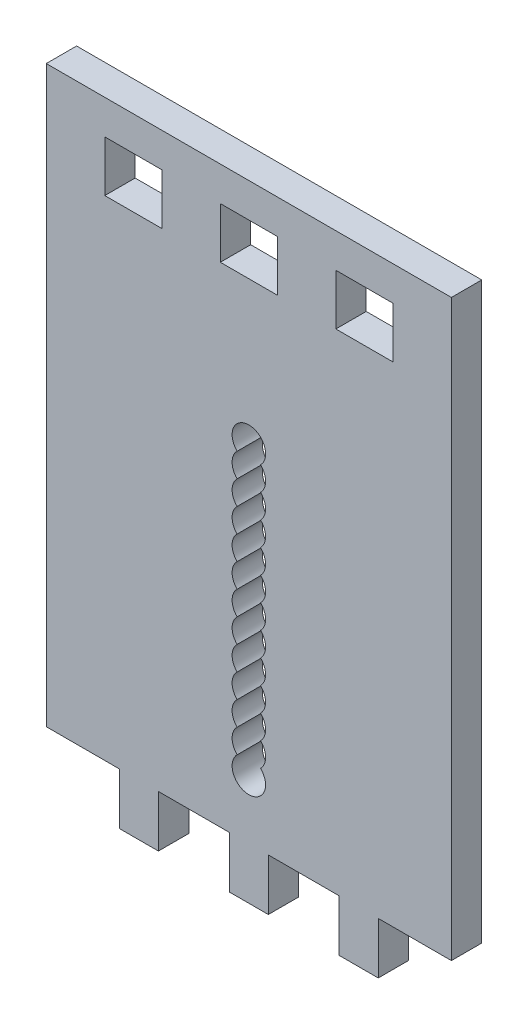
SolidWorks part; units mm, degrees
ref_plane "Front Plane" through (0, 0, 0) normal (0, 0, 1) x (1, 0, 0)
ref_plane "Top Plane" through (0, 0, 0) normal (0, 1, 0) x (1, 0, 0)
ref_plane "Right Plane" through (0, 0, 0) normal (1, 0, 0) x (0, 0, -1)
sketch "Sketch1" plane through (0, 0, 0) normal (0, 0, 1) x (1, 0, 0)
  line L0 (-21.15, 21.15) -> (21.15, 21.15) construction
  line L1 (-21.15, 38.85) -> (21.15, 38.85)
  line L2 (-21.15, 38.85) -> (-21.15, -21.15)
  line L3 (-21.15, -21.15) -> (21.15, -21.15)
  line L4 (21.15, 38.85) -> (21.15, -21.15)
  line L5 (2, -26.55) -> (2, -21.15)
  line L6 (-13.5, -21.15) -> (-9.5, -21.15)
  line L7 (-13.5, -21.15) -> (-13.5, -26.55)
  line L8 (-13.5, -26.55) -> (-9.5, -26.55)
  line L9 (-9.5, -21.15) -> (-9.5, -26.55)
  line L10 (2, -26.55) -> (-2, -26.55)
  line L11 (2, -21.15) -> (-2, -21.15)
  line L12 (-2, -26.55) -> (-2, -21.15)
  line L13 (2, -26.55) -> (-2, -21.15) construction
  line L14 (2, -21.15) -> (-2, -26.55) construction
  line L15 (-21.15, 8.85) -> (21.15, 8.85) construction
  line L16 (13.5, -21.15) -> (9.5, -21.15)
  line L17 (13.5, -21.15) -> (13.5, -26.55)
  line L18 (13.5, -26.55) -> (9.5, -26.55)
  line L19 (9.5, -21.15) -> (9.5, -26.55)
  line L21 (-15.1071, 35.35) -> (-9.0643, 35.35)
  line L22 (-15.1071, 35.35) -> (-15.1071, 29.95)
  line L23 (-15.1071, 29.95) -> (-9.0643, 29.95)
  line L24 (-9.0643, 35.35) -> (-9.0643, 29.95)
  line L25 (-3.0214, 35.35) -> (3.0214, 35.35)
  line L26 (-3.0214, 35.35) -> (-3.0214, 29.95)
  line L27 (-3.0214, 29.95) -> (3.0214, 29.95)
  line L28 (3.0214, 35.35) -> (3.0214, 29.95)
  line L29 (9.0643, 35.35) -> (15.1071, 35.35)
  line L30 (9.0643, 35.35) -> (9.0643, 29.95)
  line L31 (9.0643, 29.95) -> (15.1071, 29.95)
  line L32 (0, 15) -> (0, -15) construction
  line L33 (-0.75, 15) -> (0.75, 15)
  line L34 (-0.75, 15) -> (-0.75, -15)
  line L35 (-0.75, -15) -> (0.75, -15)
  line L36 (0.75, 15) -> (0.75, -15)
  line L37 (15.1071, 35.35) -> (15.1071, 29.95)
  arc A1 (-0.75, 15) -> (0.75, 15) centre (0, 15) cw
  arc A2 (0.75, -15) -> (-0.75, -15) centre (0, -15) cw
  circle A3 centre (0, 15) radius 1.75
  circle A4 centre (0, 12.5) radius 1.75
  circle A5 centre (0, 10) radius 1.75
  circle A6 centre (0, 7.5) radius 1.75
  circle A7 centre (0, 5) radius 1.75
  circle A8 centre (0, 2.5) radius 1.75
  circle A9 centre (0, 0) radius 1.75
  circle A10 centre (0, -2.5) radius 1.75
  circle A11 centre (0, -5) radius 1.75
  circle A12 centre (0, -7.5) radius 1.75
  circle A13 centre (0, -10) radius 1.75
  circle A14 centre (0, -12.5) radius 1.75
  circle A15 centre (0, -15) radius 1.75
  point P13 (0, -21.15)
  point P14 (0, -23.85)
  dimension "D15" = 3.5
  dimension "D1" = 42.3
  dimension "D3" = 42.3
  dimension "D4" = 21.15
  dimension "D5" = 21.15
  dimension "D2" = 60
  dimension "D8" = 4
  dimension "D6" = 1.5
  dimension "D11" = 0.75
  dimension "D12" = 30
  dimension "D13" = 15
  dimension "D7" = 7.5
  dimension "D10" = 7.5
  dimension "D16" = 2.5
  dimension "D18" = 2.5
  dimension "D9" = 5.4
  dimension "D19" = 5.4
  dimension "D20" = 6.0429
  dimension "D21" = 6.0429
  dimension "D22" = 6.0429
  dimension "D23" = 6.0429
  dimension "D24" = 3.5
  dimension "D14" = 10
  dimension "D17" = 4
extrude "Boss-Extrude1" add sketch "Sketch1" along normal blind 3.175 contours L4 L1 L2 L3 L36 A2 L34 A1 | L1 | L1 | L1 | L9 L3 L7 L8 | L3 L19 L18 L17 | L12 L10 L5 L3 region at (0, 38.1159, 0) region at (-11.5, -23.85, 0) region at (11.5, -23.85, 0) region at (0, -23.85, 0)
sketch "Sketch2" plane through (0, 0, 3.175) normal (0, 0, 1) x (1, 0, 0)
  line L2 (-15.1071, 35.3094) -> (-9.0643, 35.3094)
  line L3 (-15.1071, 35.3094) -> (-9.0643, 35.3094)
  line L5 (-15.0665, 35.35) -> (-15.0665, 29.95)
  line L6 (-15.0665, 35.35) -> (-15.0665, 29.95)
  line L7 (9.1049, 35.35) -> (9.1049, 29.95)
  line L8 (-15.1071, 29.9906) -> (-9.0643, 29.9906)
  line L9 (-15.1071, 29.9906) -> (-9.0643, 29.9906)
  line L10 (9.1049, 35.35) -> (9.1049, 29.95)
  line L11 (-9.1049, 35.35) -> (-9.1049, 29.95)
  line L12 (-9.1049, 35.35) -> (-9.1049, 29.95)
  line L14 (-2.9808, 35.35) -> (-2.9808, 29.95)
  line L15 (-2.9808, 35.35) -> (-2.9808, 29.95)
  line L16 (9.0643, 35.3094) -> (15.1071, 35.3094)
  line L17 (9.0643, 35.3094) -> (15.1071, 35.3094)
  line L18 (-3.0214, 35.3094) -> (3.0214, 35.3094)
  line L19 (-3.0214, 35.3094) -> (3.0214, 35.3094)
  line L21 (-3.0214, 29.9906) -> (3.0214, 29.9906)
  line L22 (-3.0214, 29.9906) -> (3.0214, 29.9906)
  line L24 (2.9808, 35.35) -> (2.9808, 29.95)
  line L25 (2.9808, 35.35) -> (2.9808, 29.95)
  line L26 (9.0643, 29.9906) -> (15.1071, 29.9906)
  line L27 (9.0643, 29.9906) -> (15.1071, 29.9906)
  line L29 (15.0665, 35.35) -> (15.0665, 29.95)
  line L30 (15.0665, 35.35) -> (15.0665, 29.95)
  line L32 (21.1906, -21.1906) -> (21.1906, 38.8906)
  line L33 (21.1906, 38.8906) -> (-21.1906, 38.8906)
  line L34 (-21.1906, 38.8906) -> (-21.1906, -21.1906)
  line L35 (-21.1906, -21.1906) -> (-13.5406, -21.1906)
  line L36 (-13.5406, -21.1906) -> (-13.5406, -26.5906)
  line L37 (-13.5406, -26.5906) -> (-9.4594, -26.5906)
  line L38 (-9.4594, -26.5906) -> (-9.4594, -21.1906)
  line L39 (-9.4594, -21.1906) -> (-2.0406, -21.1906)
  line L40 (-2.0406, -21.1906) -> (-2.0406, -26.5906)
  line L41 (-2.0406, -26.5906) -> (2.0406, -26.5906)
  line L42 (2.0406, -26.5906) -> (2.0406, -21.1906)
  line L43 (2.0406, -21.1906) -> (9.4594, -21.1906)
  line L44 (9.4594, -21.1906) -> (9.4594, -26.5906)
  line L45 (9.4594, -26.5906) -> (13.5406, -26.5906)
  line L46 (13.5406, -26.5906) -> (13.5406, -21.1906)
  line L47 (13.5406, -21.1906) -> (21.1906, -21.1906)
  line L48 (21.1906, -21.1906) -> (21.1906, 38.8906)
  line L49 (21.1906, 38.8906) -> (-21.1906, 38.8906)
  line L50 (-21.1906, 38.8906) -> (-21.1906, -21.1906)
  line L51 (-21.1906, -21.1906) -> (-13.5406, -21.1906)
  line L52 (-13.5406, -21.1906) -> (-13.5406, -26.5906)
  line L53 (-13.5406, -26.5906) -> (-9.4594, -26.5906)
  line L54 (-9.4594, -26.5906) -> (-9.4594, -21.1906)
  line L55 (-9.4594, -21.1906) -> (-2.0406, -21.1906)
  line L56 (-2.0406, -21.1906) -> (-2.0406, -26.5906)
  line L57 (-2.0406, -26.5906) -> (2.0406, -26.5906)
  line L58 (2.0406, -26.5906) -> (2.0406, -21.1906)
  line L59 (2.0406, -21.1906) -> (9.4594, -21.1906)
  line L60 (9.4594, -21.1906) -> (9.4594, -26.5906)
  line L61 (9.4594, -26.5906) -> (13.5406, -26.5906)
  line L62 (13.5406, -26.5906) -> (13.5406, -21.1906)
  line L63 (13.5406, -21.1906) -> (21.1906, -21.1906)
  arc A2 (1.2247, 13.75) -> (-1.2247, 13.75) centre (0, 15) ccw
  arc A3 (1.2247, 13.75) -> (-1.2247, 13.75) centre (0, 15) ccw
  arc A5 (-1.2247, 13.75) -> (-1.2247, 11.25) centre (0, 12.5) ccw
  arc A6 (-1.2247, 13.75) -> (-1.2247, 11.25) centre (0, 12.5) ccw
  arc A8 (1.2247, 11.25) -> (1.2247, 13.75) centre (0, 12.5) ccw
  arc A9 (1.2247, 11.25) -> (1.2247, 13.75) centre (0, 12.5) ccw
  arc A11 (-1.2247, 11.25) -> (-1.2247, 8.75) centre (0, 10) ccw
  arc A12 (-1.2247, 11.25) -> (-1.2247, 8.75) centre (0, 10) ccw
  arc A14 (1.2247, 8.75) -> (1.2247, 11.25) centre (0, 10) ccw
  arc A15 (1.2247, 8.75) -> (1.2247, 11.25) centre (0, 10) ccw
  arc A17 (-1.2247, 8.75) -> (-1.2247, 6.25) centre (0, 7.5) ccw
  arc A18 (-1.2247, 8.75) -> (-1.2247, 6.25) centre (0, 7.5) ccw
  arc A20 (1.2247, 6.25) -> (1.2247, 8.75) centre (0, 7.5) ccw
  arc A21 (1.2247, 6.25) -> (1.2247, 8.75) centre (0, 7.5) ccw
  arc A23 (-1.2247, 6.25) -> (-1.2247, 3.75) centre (0, 5) ccw
  arc A24 (-1.2247, 6.25) -> (-1.2247, 3.75) centre (0, 5) ccw
  arc A26 (1.2247, 3.75) -> (1.2247, 6.25) centre (0, 5) ccw
  arc A27 (1.2247, 3.75) -> (1.2247, 6.25) centre (0, 5) ccw
  arc A29 (-1.2247, 3.75) -> (-1.2247, 1.25) centre (0, 2.5) ccw
  arc A30 (-1.2247, 3.75) -> (-1.2247, 1.25) centre (0, 2.5) ccw
  arc A32 (1.2247, 1.25) -> (1.2247, 3.75) centre (0, 2.5) ccw
  arc A33 (1.2247, 1.25) -> (1.2247, 3.75) centre (0, 2.5) ccw
  arc A35 (-1.2247, 1.25) -> (-1.2247, -1.25) centre (0, 0) ccw
  arc A36 (-1.2247, 1.25) -> (-1.2247, -1.25) centre (0, 0) ccw
  arc A38 (1.2247, -1.25) -> (1.2247, 1.25) centre (0, 0) ccw
  arc A39 (1.2247, -1.25) -> (1.2247, 1.25) centre (0, 0) ccw
  arc A42 (1.2247, -3.75) -> (1.2247, -1.25) centre (0, -2.5) ccw
  arc A43 (1.2247, -3.75) -> (1.2247, -1.25) centre (0, -2.5) ccw
  arc A45 (-1.2247, -1.25) -> (-1.2247, -3.75) centre (0, -2.5) ccw
  arc A46 (-1.2247, -1.25) -> (-1.2247, -3.75) centre (0, -2.5) ccw
  arc A48 (-1.2247, -3.75) -> (-1.2247, -6.25) centre (0, -5) ccw
  arc A49 (-1.2247, -3.75) -> (-1.2247, -6.25) centre (0, -5) ccw
  arc A51 (1.2247, -6.25) -> (1.2247, -3.75) centre (0, -5) ccw
  arc A52 (1.2247, -6.25) -> (1.2247, -3.75) centre (0, -5) ccw
  arc A55 (-1.2247, -6.25) -> (-1.2247, -8.75) centre (0, -7.5) ccw
  arc A56 (-1.2247, -6.25) -> (-1.2247, -8.75) centre (0, -7.5) ccw
  arc A58 (1.2247, -8.75) -> (1.2247, -6.25) centre (0, -7.5) ccw
  arc A59 (1.2247, -8.75) -> (1.2247, -6.25) centre (0, -7.5) ccw
  arc A61 (-1.2247, -8.75) -> (-1.2247, -11.25) centre (0, -10) ccw
  arc A62 (-1.2247, -8.75) -> (-1.2247, -11.25) centre (0, -10) ccw
  arc A64 (1.2247, -11.25) -> (1.2247, -8.75) centre (0, -10) ccw
  arc A65 (1.2247, -11.25) -> (1.2247, -8.75) centre (0, -10) ccw
  arc A67 (-1.2247, -11.25) -> (-1.2247, -13.75) centre (0, -12.5) ccw
  arc A68 (-1.2247, -11.25) -> (-1.2247, -13.75) centre (0, -12.5) ccw
  arc A70 (1.2247, -13.75) -> (1.2247, -11.25) centre (0, -12.5) ccw
  arc A71 (1.2247, -13.75) -> (1.2247, -11.25) centre (0, -12.5) ccw
  arc A73 (-1.2247, -13.75) -> (1.2247, -13.75) centre (0, -15) ccw
  arc A74 (-1.2247, -13.75) -> (1.2247, -13.75) centre (0, -15) ccw
  dimension "D1" = 0.0406
  dimension "D2" = 0.0406
  dimension "D3" = 0.0406
  dimension "D4" = 0.0406
  dimension "D5" = 0.0406
  dimension "D6" = 0.0406
  dimension "D7" = 0.0406
  dimension "D8" = 0.0406
  dimension "D9" = 0.0406
  dimension "D10" = 0.0406
  dimension "D11" = 0.0406
  dimension "D12" = 0.0406
  dimension "D13" = 0.0406
  dimension "D14" = 0
  dimension "D15" = 0
  dimension "D16" = 0
  dimension "D17" = 0
  dimension "D18" = 0
  dimension "D19" = 0
  dimension "D20" = 0
  dimension "D21" = 0
  dimension "D22" = 0
  dimension "D23" = 0
  dimension "D24" = 0
  dimension "D25" = 0
  dimension "D26" = 0
  dimension "D27" = 0
  dimension "D28" = 0
  dimension "D29" = 0
  dimension "D30" = 0
  dimension "D31" = 0
  dimension "D32" = 0
  dimension "D33" = 0
  dimension "D34" = 0
  dimension "D35" = 0
  dimension "D36" = 0
  dimension "D37" = 0
extrude "Boss-Extrude2" add sketch "Sketch2" against normal up to surface (3.175 mm away) contours L62 L63 L48 L49 L50 L51 L52 L53 L54 L55 L56 L57 L58 L59 L60 L61 A74 A68 A62 A56 A49 A46 A36 A30 A24 A18 A12 A6 A3 A9 A15 A21 A27 A33 A39 A43 A52 A59 A65 A71 L30 L27 region at (17.3656, -20.4106, 3.175) up to face at (0, 0, 0)
equation "\"stepper width\"=4.23"
equation "\"stepper hole disctance\"= 3.1"
equation "\"stepper hole diameter\"=0.34"
equation "\"stepper shaft hole\"=2.4"
equation "\"tooth width\"=0.4"
equation "\"tooth thickness\"=0.3175"
equation "\"tooth to side\"=0.75"
equation "\"motor chamber height\"= 6"
equation "\"D1@Sketch1\"=\"stepper width\""
equation "\"D3@Sketch1\"=\"stepper width\""
equation "\"D4@Sketch1\"=\"stepper width\"/2"
equation "\"D5@Sketch1\"=\"stepper width\"/2"
equation "\"gear shaft diameter\"=0.15"
equation "\"D2@Sketch1\"=\"motor chamber height\""
equation "\"D8@Sketch1\"=\"tooth width\""
equation "\"D1@Boss-Extrude1\"=\"tooth thickness\""
equation "\"D6@Sketch1\"=\"gear shaft diameter\""
equation "\"D11@Sketch1\"=\"gear shaft diameter\"/2"
equation "\"D12@Sketch1\"=\"motor chamber height\"/2"
equation "\"D13@Sketch1\"=\"motor chamber height\"/4"
equation "\"D7@Sketch1\"=\"tooth to side\""
equation "\"D10@Sketch1\"=\"tooth to side\""
equation "\"D20@Sketch1\"=\"stepper width\"/7"
equation "\"D21@Sketch1\"=\"stepper width\"/7"
equation "\"D22@Sketch1\"=\"stepper width\"/7"
equation "\"D23@Sketch1\"=\"stepper width\"/7"
equation "\"D5@Sketch1\"=\"stepper hole diameter\""
